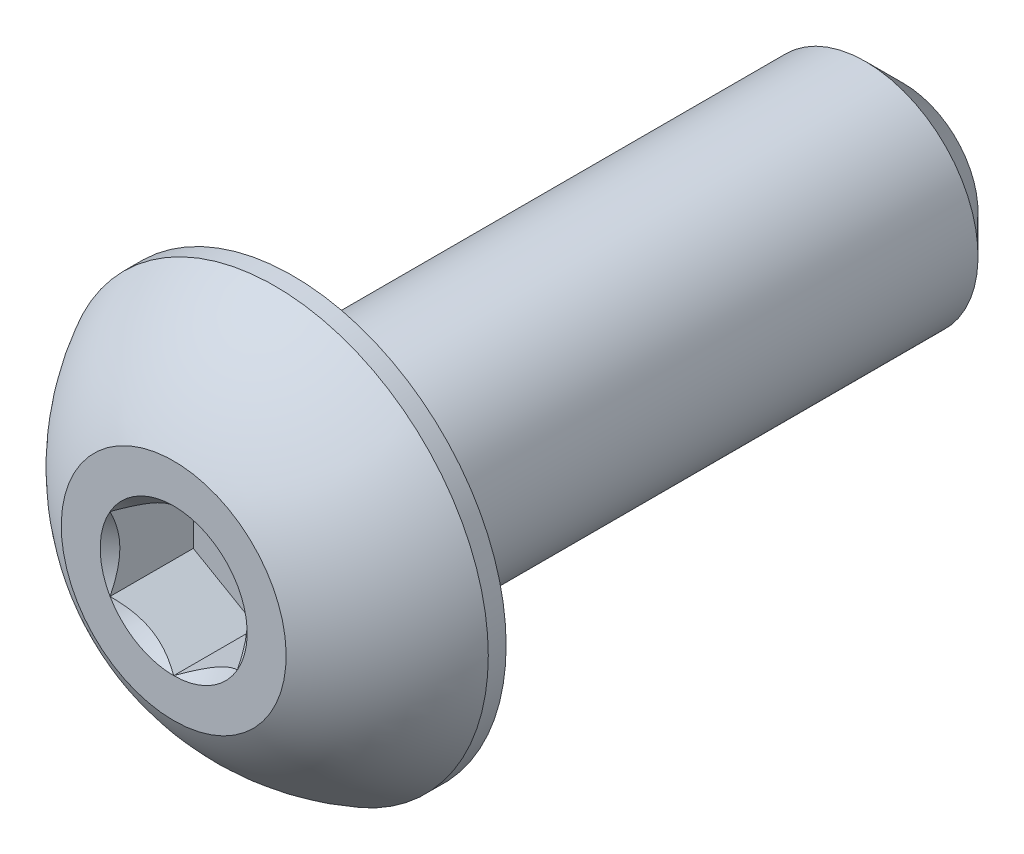
SolidWorks part; units mm, degrees
ref_plane "Front" through (0, 0, 0) normal (0, 0, 1) x (1, 0, 0)
ref_plane "Top" through (0, 0, 0) normal (0, 1, 0) x (1, 0, 0)
ref_plane "Right" through (0, 0, 0) normal (1, 0, 0) x (0, 0, -1)
sketch "Sketch1" plane through (0, 0, 0) normal (1, 0, 0) x (0, 0, -1)
  line L2 (1.8542, 1.7526) -> (11.3792, 1.7526)
  line L3 (11.3792, 1.7526) -> (11.3792, 0)
  line L4 (11.3792, 0) -> (1.8542, 0)
  line L6 (1.5761, 3.3274) -> (1.8542, 3.3274) construction
  line L7 (11.3792, 1.7526) -> (11.3792, -1.7526) construction
  line L8 (0, 0) -> (1.8542, 0) construction
  line L9 (1.8542, 3.3274) -> (1.8542, -3.3274) construction
  line L11 (1.8542, 1.7526) -> (1.8542, 0)
  line L13 (0, 0.9922) -> (0, -0.9922) construction
  line L14 (0, 0.9922) -> (0, 1.7526) construction
  arc A3 (0, 1.7526) -> (1.5761, 3.3274) centre (3.326, 0) cw construction
  dimension "D1" = 0.2781
revolve "Revolve1" add sketch "Sketch1" angle 360 mid plane about L4
sketch "Sketch3" plane through (0, 0, -11.3792) normal (0, 0, -1) x (-1, 0, 0)
  circle A0 centre (0, 0) radius 1.7526
curve "Helix/Spiral1" [suppressed] pitch 0.7937 height 10.3188 turns 13
sketch "Sketch2" plane through (0, 0, 0) normal (1, 0, 0) x (0, 0, -1)
  line L0 (11.3792, 1.7526) -> (12.0737, 1.7526)
  line L1 (12.0737, 1.7526) -> (11.7761, 1.237)
  line L2 (11.7761, 1.237) -> (11.6769, 1.237)
  line L3 (11.6769, 1.237) -> (11.3792, 1.7526)
  line L4 (11.528, 1.4948) -> (11.9249, 1.4948) construction
  dimension "D1" = 60
  dimension "D2" = 0.0992
  dimension "D3" = 0.3969
chamfer "Chamfer1" distance 0.5953 angle 45 1 edges at (0, 1.7526, -11.3792)
sweep "Cut-Sweep1" [suppressed] cut profiles "Sketch2" path "Helix/Spiral1"
sketch "Sketch7" plane through (0, 0, 0) normal (1, 0, 0) x (0, 0, -1)
  line L6 (1.5761, 3.3274) -> (1.8542, 3.3274) construction
  line L8 (0, 0) -> (1.8542, 0) construction
  line L11 (1.8542, 3.3274) -> (1.8542, -3.3274) construction
  line L12 (1.5761, 3.3274) -> (1.8542, 3.3274)
  line L13 (0, 0) -> (1.8542, 0)
  line L14 (0, 0.9922) -> (0, -0.9922) construction
  line L15 (1.8542, 3.3274) -> (1.8542, 0)
  line L16 (0, 1.7526) -> (0, 0)
  arc A2 (1.5761, 3.3274) -> (0, 1.7526) centre (3.326, 0) ccw construction
  arc A3 (1.5761, 3.3274) -> (0, 1.7526) centre (3.326, 0) ccw
revolve "Revolve2" add sketch "Sketch7" angle 360 mid plane about L13
sketch "Sketch5" plane through (0, 0, 0) normal (0, 0, 1) x (1, 0, 0)
  line L1 (0.9922, -0.5728) -> (0.9922, 0.5728)
  line L2 (0.9922, 0.5728) -> (0, 1.1457)
  line L3 (0, 1.1457) -> (-0.9922, 0.5728)
  line L4 (-0.9922, 0.5728) -> (-0.9922, -0.5728)
  line L5 (-0.9922, -0.5728) -> (0, -1.1457)
  line L6 (0, -1.1457) -> (0.9922, -0.5728)
  circle A0 centre (0, 0) radius 0.9922 construction
extrude "Cut-Extrude2" cut sketch "Sketch5" against normal blind 1.2979
sketch "Sketch6" plane through (0, 0, 0) normal (0, 0, 1) x (1, 0, 0)
  circle A0 centre (0, 0) radius 1.1457
extrude "Cut-Extrude3" cut sketch "Sketch6" against normal blind 1.2979 draft 45
sketch "Sketch9" [suppressed] plane through (0, 0, -1.4986) normal (0, 0, 1) x (1, 0, 0)
  circle A2 centre (0, 0) radius 1.4224
extrude "Boss-Extrude2" [suppressed] add sketch "Sketch9" against normal offset from surface (12.7 mm away) 31.75
sketch "Sketch10" plane through (0, 0, 0) normal (1, 0, 0) x (0, 0, -1)
  line L0 (11.3792, 1.7526) -> (11.3792, -1.7526) construction
  point P0 (10.1886, -1.7526)
  dimension "D1" = 1.1906
equation "\"D3@Helix/Spiral1\" = \"Lg@Sketch1\" + \"D4@Helix/Spiral1\""
equation "\"D2@Sketch2\" = \"D4@Helix/Spiral1\" * .125"
equation "\"D3@Sketch2\" = \"D4@Helix/Spiral1\" * .5"
equation "\"D1@Chamfer1\" = \"D4@Helix/Spiral1\" * .75"
equation "\"D1@Cut-Extrude2\" = \"Head Ht@Sketch1\" * .7"
equation "\"D1@Sketch1\" = \"Head Ht@Sketch1\" * .15"
equation "\"D1@Sketch10\" = \"D4@Helix/Spiral1\" * 1.5"
equation "\"D1@Cut-Extrude3\" = \"D1@Cut-Extrude2\""
